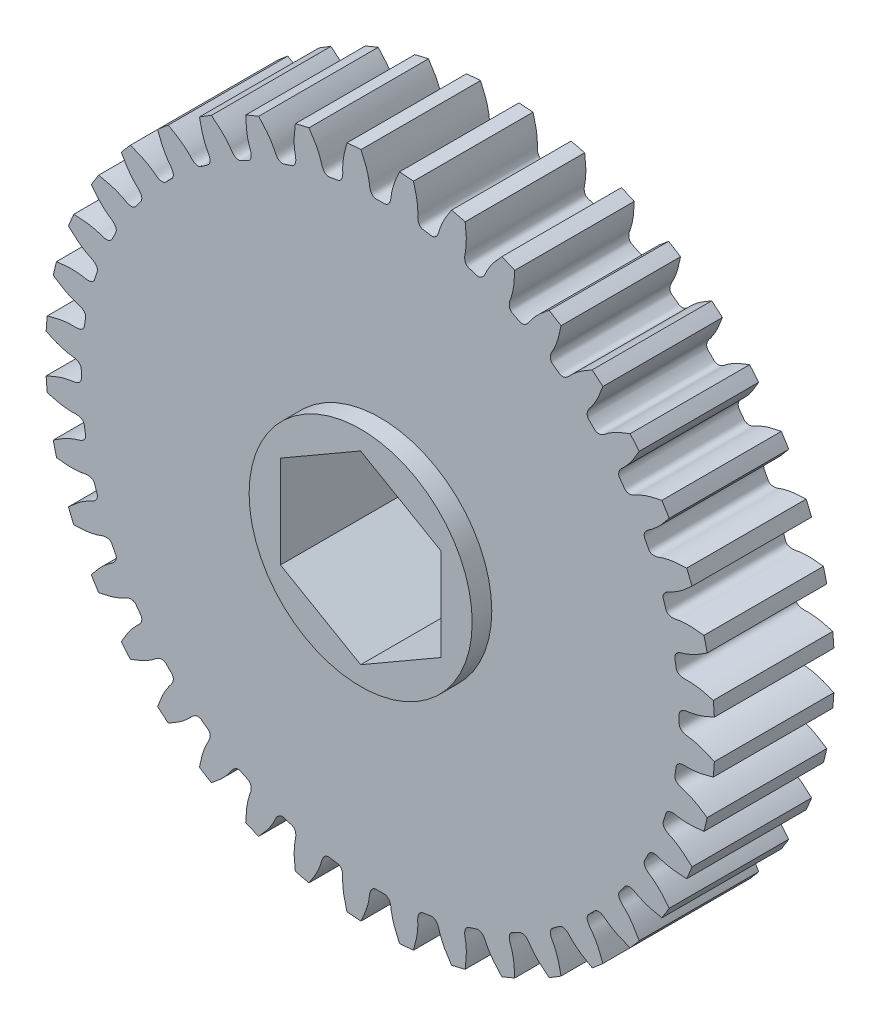
SolidWorks part; units mm, degrees
material "7075-T6 (SN)"
ref_plane "Front Plane" through (0, 0, 0) normal (0, 0, 1) x (1, 0, 0)
ref_plane "Top Plane" through (0, 0, 0) normal (0, 1, 0) x (1, 0, 0)
ref_plane "Right Plane" through (0, 0, 0) normal (1, 0, 0) x (0, 0, -1)
ref_plane "Plane1" through (0, 0, -4.7625) normal (0, 0, -1) x (-1, 0, 0)
sketch "Sketch1" plane through (0, 0, -4.7625) normal (0, 0, -1) x (-1, 0, 0)
  arc A0 (-25.7968, 6.7684) -> (-26.058, 5.6808) centre (0, 0) ccw
  arc A1 (-26.5381, 2.6496) -> (-26.6258, 1.5345) centre (0, 0) ccw
  arc A2 (-26.6258, -1.5345) -> (-26.5381, -2.6496) centre (0, 0) ccw
  arc A3 (-26.058, -5.6808) -> (-25.7968, -6.7684) centre (0, 0) ccw
  arc A4 (-24.8485, -9.6872) -> (-24.4204, -10.7206) centre (0, 0) ccw
  arc A5 (-23.0271, -13.4551) -> (-22.4427, -14.4088) centre (0, 0) ccw
  arc A6 (-20.6388, -16.8917) -> (-19.9124, -17.7422) centre (0, 0) ccw
  arc A7 (-17.7422, -19.9124) -> (-16.8917, -20.6388) centre (0, 0) ccw
  arc A8 (-14.4088, -22.4427) -> (-13.4551, -23.0271) centre (0, 0) ccw
  arc A9 (-10.7206, -24.4204) -> (-9.6872, -24.8485) centre (0, 0) ccw
  arc A10 (-6.7684, -25.7968) -> (-5.6808, -26.058) centre (0, 0) ccw
  arc A11 (-2.6496, -26.5381) -> (-1.5345, -26.6258) centre (0, 0) ccw
  arc A12 (1.5345, -26.6258) -> (2.6496, -26.5381) centre (0, 0) ccw
  arc A13 (5.6808, -26.058) -> (6.7684, -25.7968) centre (0, 0) ccw
  arc A14 (9.6872, -24.8485) -> (10.7206, -24.4204) centre (0, 0) ccw
  arc A15 (13.4551, -23.0271) -> (14.4088, -22.4427) centre (0, 0) ccw
  arc A16 (16.8917, -20.6388) -> (17.7422, -19.9124) centre (0, 0) ccw
  arc A17 (19.9124, -17.7422) -> (20.6388, -16.8917) centre (0, 0) ccw
  arc A18 (22.4427, -14.4088) -> (23.0271, -13.4551) centre (0, 0) ccw
  arc A19 (24.4204, -10.7206) -> (24.8485, -9.6872) centre (0, 0) ccw
  arc A20 (25.7968, -6.7684) -> (26.058, -5.6808) centre (0, 0) ccw
  arc A21 (26.5381, -2.6496) -> (26.6258, -1.5345) centre (0, 0) ccw
  arc A22 (26.6258, 1.5345) -> (26.5381, 2.6496) centre (0, 0) ccw
  arc A23 (26.058, 5.6808) -> (25.7968, 6.7684) centre (0, 0) ccw
  arc A24 (24.8485, 9.6872) -> (24.4204, 10.7206) centre (0, 0) ccw
  arc A25 (23.0271, 13.4551) -> (22.4427, 14.4088) centre (0, 0) ccw
  arc A26 (20.6388, 16.8917) -> (19.9124, 17.7422) centre (0, 0) ccw
  arc A27 (17.7422, 19.9124) -> (16.8917, 20.6388) centre (0, 0) ccw
  arc A28 (14.4088, 22.4427) -> (13.4551, 23.0271) centre (0, 0) ccw
  arc A29 (10.7206, 24.4204) -> (9.6872, 24.8485) centre (0, 0) ccw
  arc A30 (6.7684, 25.7968) -> (5.6808, 26.058) centre (0, 0) ccw
  arc A31 (2.6496, 26.5381) -> (1.5345, 26.6258) centre (0, 0) ccw
  arc A32 (-1.5345, 26.6258) -> (-2.6496, 26.5381) centre (0, 0) ccw
  arc A33 (-5.6808, 26.058) -> (-6.7684, 25.7968) centre (0, 0) ccw
  arc A34 (-9.6872, 24.8485) -> (-10.7206, 24.4204) centre (0, 0) ccw
  arc A35 (-13.4551, 23.0271) -> (-14.4088, 22.4427) centre (0, 0) ccw
  arc A36 (-16.8917, 20.6388) -> (-17.7422, 19.9124) centre (0, 0) ccw
  arc A37 (-19.9124, 17.7422) -> (-20.6388, 16.8917) centre (0, 0) ccw
  arc A38 (-22.4427, 14.4088) -> (-23.0271, 13.4551) centre (0, 0) ccw
  arc A39 (-24.4204, 10.7206) -> (-24.8485, 9.6872) centre (0, 0) ccw
  spline S0 degree 3 number of poles 87 (-25.7968, 6.7684) -> (-24.8485, 9.6872)
  spline S1 degree 3 number of poles 87 (-26.5381, 2.6496) -> (-26.058, 5.6808)
  spline S2 degree 3 number of poles 87 (-26.6258, -1.5345) -> (-26.6258, 1.5345)
  spline S3 degree 3 number of poles 87 (-26.058, -5.6808) -> (-26.5381, -2.6496)
  spline S4 degree 3 number of poles 87 (-24.8485, -9.6872) -> (-25.7968, -6.7684)
  spline S5 degree 3 number of poles 87 (-23.0271, -13.4551) -> (-24.4204, -10.7206)
  spline S6 degree 3 number of poles 87 (-20.6388, -16.8917) -> (-22.4427, -14.4088)
  spline S7 degree 3 number of poles 87 (-17.7422, -19.9124) -> (-19.9124, -17.7422)
  spline S8 degree 3 number of poles 87 (-14.4088, -22.4427) -> (-16.8917, -20.6388)
  spline S9 degree 3 number of poles 87 (-10.7206, -24.4204) -> (-13.4551, -23.0271)
  spline S10 degree 3 number of poles 87 (-6.7684, -25.7968) -> (-9.6872, -24.8485)
  spline S11 degree 3 number of poles 87 (-2.6496, -26.5381) -> (-5.6808, -26.058)
  spline S12 degree 3 number of poles 87 (1.5345, -26.6258) -> (-1.5345, -26.6258)
  spline S13 degree 3 number of poles 87 (5.6808, -26.058) -> (2.6496, -26.5381)
  spline S14 degree 3 number of poles 87 (9.6872, -24.8485) -> (6.7684, -25.7968)
  spline S15 degree 3 number of poles 87 (13.4551, -23.0271) -> (10.7206, -24.4204)
  spline S16 degree 3 number of poles 87 (16.8917, -20.6388) -> (14.4088, -22.4427)
  spline S17 degree 3 number of poles 87 (19.9124, -17.7422) -> (17.7422, -19.9124)
  spline S18 degree 3 number of poles 87 (22.4427, -14.4088) -> (20.6388, -16.8917)
  spline S19 degree 3 number of poles 87 (24.4204, -10.7206) -> (23.0271, -13.4551)
  spline S20 degree 3 number of poles 87 (25.7968, -6.7684) -> (24.8485, -9.6872)
  spline S21 degree 3 number of poles 87 (26.5381, -2.6496) -> (26.058, -5.6808)
  spline S22 degree 3 number of poles 87 (26.6258, 1.5345) -> (26.6258, -1.5345)
  spline S23 degree 3 number of poles 87 (26.058, 5.6808) -> (26.5381, 2.6496)
  spline S24 degree 3 number of poles 87 (24.8485, 9.6872) -> (25.7968, 6.7684)
  spline S25 degree 3 number of poles 87 (23.0271, 13.4551) -> (24.4204, 10.7206)
  spline S26 degree 3 number of poles 87 (20.6388, 16.8917) -> (22.4427, 14.4088)
  spline S27 degree 3 number of poles 87 (17.7422, 19.9124) -> (19.9124, 17.7422)
  spline S28 degree 3 number of poles 87 (14.4088, 22.4427) -> (16.8917, 20.6388)
  spline S29 degree 3 number of poles 87 (10.7206, 24.4204) -> (13.4551, 23.0271)
  spline S30 degree 3 number of poles 87 (6.7684, 25.7968) -> (9.6872, 24.8485)
  spline S31 degree 3 number of poles 87 (2.6496, 26.5381) -> (5.6808, 26.058)
  spline S32 degree 3 number of poles 87 (-1.5345, 26.6258) -> (1.5345, 26.6258)
  spline S33 degree 3 number of poles 87 (-5.6808, 26.058) -> (-2.6496, 26.5381)
  spline S34 degree 3 number of poles 87 (-9.6872, 24.8485) -> (-6.7684, 25.7968)
  spline S35 degree 3 number of poles 87 (-13.4551, 23.0271) -> (-10.7206, 24.4204)
  spline S36 degree 3 number of poles 87 (-16.8917, 20.6388) -> (-14.4088, 22.4427)
  spline S37 degree 3 number of poles 87 (-19.9124, 17.7422) -> (-17.7422, 19.9124)
  spline S38 degree 3 number of poles 87 (-22.4427, 14.4088) -> (-20.6388, 16.8917)
  spline S39 degree 3 number of poles 87 (-24.4204, 10.7206) -> (-23.0271, 13.4551)
extrude "Boss-Extrude1" add sketch "Sketch1" against normal blind 9.525
sketch "Sketch2" plane through (0, 0, -4.7625) normal (0, 0, -1) x (-1, 0, 0)
  circle A0 centre (0, 0) radius 8.89
extrude "Boss-Extrude2" add sketch "Sketch2" along normal blind 1.5621
sketch "Sketch3" plane through (0, 0, 4.7625) normal (0, 0, 1) x (1, 0, 0)
  circle A0 centre (0, 0) radius 8.89
extrude "Boss-Extrude3" add sketch "Sketch3" along normal blind 1.5621
sketch "Sketch4" plane through (0, 0, 6.3246) normal (0, 0, 1) x (1, 0, 0)
  line L0 (6.3881, -3.6882) -> (6.3881, 3.6882)
  line L1 (6.3881, 3.6882) -> (0, 7.3763)
  line L2 (0, 7.3763) -> (-6.3881, 3.6882)
  line L3 (-6.3881, 3.6882) -> (-6.3881, -3.6882)
  line L4 (-6.3881, -3.6882) -> (0, -7.3763)
  line L5 (0, -7.3763) -> (6.3881, -3.6882)
extrude "Cut-Extrude1" cut sketch "Sketch4" against normal through all
ref_axis "Center Axis" through (0, 0, 8.6469) along (0, 0, -1)
